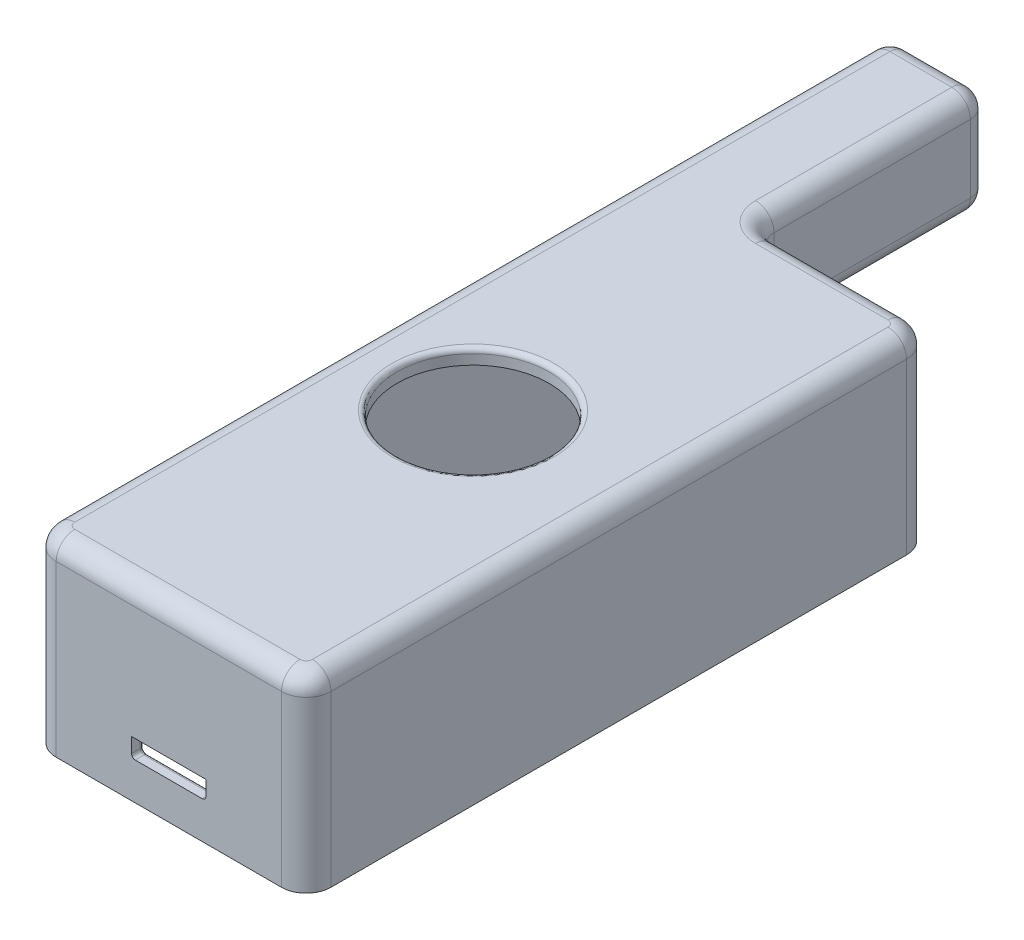
SolidWorks part; units mm, degrees
ref_plane "Front Plane" through (0, 0, 0) normal (0, 0, 1) x (1, 0, 0)
ref_plane "Top Plane" through (0, 0, 0) normal (0, 1, 0) x (1, 0, 0)
ref_plane "Right Plane" through (0, 0, 0) normal (1, 0, 0) x (0, 0, -1)
sketch "Esquisse1" plane through (0, 0, 0) normal (0, 1, 0) x (1, 0, 0)
  line L0 (-10.0853, 24.1442) -> (-10.0853, 42.1442)
  line L1 (-3.0853, 24.2853) -> (9.1147, 24.2853)
  line L2 (-10.0853, 24.1442) -> (-10.0853, -23.2147)
  line L3 (-9.0853, -24.2147) -> (9.1147, -24.2147)
  line L4 (10.1147, 23.2853) -> (10.1147, -23.2147)
  line L5 (-10.0853, 24.1442) -> (10.1147, -24.2147) construction
  line L6 (-10.0853, -24.2147) -> (10.1147, 24.2853) construction
  line L7 (-9.0853, 43.1442) -> (-5.0853, 43.1442)
  line L8 (-4.0853, 42.1442) -> (-4.0853, 25.2853)
  line L9 (-11.0853, 24.1442) -> (-11.0853, 42.1442)
  line L10 (-9.0853, 44.1442) -> (-5.0853, 44.1442)
  line L11 (-3.0853, 42.1442) -> (-3.0853, 27.2853)
  line L12 (-1.0853, 25.2853) -> (9.1147, 25.2853)
  line L13 (11.1147, 23.2853) -> (11.1147, -23.2147)
  line L14 (-9.0853, -25.2147) -> (9.1147, -25.2147)
  line L15 (-11.0853, 24.1442) -> (-11.0853, -23.2147)
  line L16 (-10.0853, 42.1442) -> (-10.0853, 43.1442)
  line L17 (-10.0853, 43.1442) -> (-9.0853, 43.1442)
  line L18 (-4.0853, 42.1442) -> (-4.0853, 43.1442)
  line L19 (-4.0853, 43.1442) -> (-5.0853, 43.1442)
  line L20 (-11.0853, 42.1442) -> (-11.0853, 44.1442)
  line L21 (-11.0853, 44.1442) -> (-9.0853, 44.1442)
  line L22 (-3.0853, 42.1442) -> (-3.0853, 44.1442)
  line L23 (-3.0853, 44.1442) -> (-5.0853, 44.1442)
  arc A0 (-10.0853, -23.2147) -> (-9.0853, -24.2147) centre (-9.0853, -23.2147) ccw
  arc A1 (9.1147, -24.2147) -> (10.1147, -23.2147) centre (9.1147, -23.2147) ccw
  arc A2 (9.1147, 24.2853) -> (10.1147, 23.2853) centre (9.1147, 23.2853) cw
  arc A3 (-4.0853, 25.2853) -> (-3.0853, 24.2853) centre (-3.0853, 25.2853) ccw
  arc A9 (9.1147, 25.2853) -> (11.1147, 23.2853) centre (9.1147, 23.2853) cw
  arc A10 (9.1147, -25.2147) -> (11.1147, -23.2147) centre (9.1147, -23.2147) ccw
  arc A11 (-11.0853, -23.2147) -> (-9.0853, -25.2147) centre (-9.0853, -23.2147) ccw
  arc A12 (-3.0853, 27.2853) -> (-1.0853, 25.2853) centre (-1.0853, 27.2853) ccw
  point P0 (0, 0)
  point P22 (-4.0853, 43.1442)
  point P25 (-10.0853, 43.1442)
  dimension "D5" = 1
  dimension "D7" = 2
  dimension "D1" = 20.2
  dimension "D2" = 48.5
  dimension "D3" = 19
  dimension "D4" = 6
extrude "Boss.-Extru.1" add sketch "Esquisse1" along normal blind 14
sketch "Esquisse2" plane through (0, 14, 0) normal (0, 1, 0) x (1, 0, 0)
  line L12 (-11.0853, 44.1442) -> (-11.0853, -23.2147)
  line L13 (-9.0853, -25.2147) -> (9.1147, -25.2147)
  line L14 (11.1147, -23.2147) -> (11.1147, 23.2853)
  line L15 (9.1147, 25.2853) -> (-1.0853, 25.2853)
  line L16 (-3.0853, 27.2853) -> (-3.0853, 44.1442)
  line L17 (-3.0853, 44.1442) -> (-11.0853, 44.1442)
  line L18 (-11.0853, 44.1442) -> (-11.0853, -23.2147)
  line L19 (-9.0853, -25.2147) -> (9.1147, -25.2147)
  line L20 (11.1147, -23.2147) -> (11.1147, 23.2853)
  line L21 (9.1147, 25.2853) -> (-1.0853, 25.2853)
  line L22 (-3.0853, 27.2853) -> (-3.0853, 44.1442)
  line L23 (-3.0853, 44.1442) -> (-11.0853, 44.1442)
  arc A12 (-11.0853, -23.2147) -> (-9.0853, -25.2147) centre (-9.0853, -23.2147) ccw
  arc A13 (9.1147, -25.2147) -> (11.1147, -23.2147) centre (9.1147, -23.2147) ccw
  arc A14 (11.1147, 23.2853) -> (9.1147, 25.2853) centre (9.1147, 23.2853) ccw
  arc A15 (-3.0853, 27.2853) -> (-1.0853, 25.2853) centre (-1.0853, 27.2853) ccw
  arc A18 (-11.0853, -23.2147) -> (-9.0853, -25.2147) centre (-9.0853, -23.2147) ccw
  arc A19 (9.1147, -25.2147) -> (11.1147, -23.2147) centre (9.1147, -23.2147) ccw
  arc A20 (11.1147, 23.2853) -> (9.1147, 25.2853) centre (9.1147, 23.2853) ccw
  arc A21 (-3.0853, 27.2853) -> (-1.0853, 25.2853) centre (-1.0853, 27.2853) ccw
  dimension "D1" = 0
extrude "Boss.-Extru.2" add sketch "Esquisse2" along normal blind 1.2
sketch "Esquisse4" plane through (0, 14, 0) normal (0, -1, 0) x (1, 0, 0)
  line L0 (-10.0853, -0.7153) -> (-1.3353, -0.7153) construction
  line L1 (-10.0853, -43.1442) -> (-10.0853, 23.2147) construction
  line L2 (-1.3353, -0.7153) -> (-1.3353, 24.2147) construction
  line L3 (-9.0853, 24.2147) -> (9.1147, 24.2147) construction
  circle A0 centre (-1.3353, -0.7153) radius 6.15
  dimension "D3" = 12.3
  dimension "D1" = 24.93
  dimension "D2" = 8.75
extrude "Enlèv. mat.-Extru.1" cut sketch "Esquisse4" against normal through all
fillet "Congé2" radius 0.4 1 edges at (-1.3353, 15.2, -6.8653)
sketch "Esquisse5" plane through (0, 14, 0) normal (0, -1, 0) x (1, 0, 0)
  line L0 (-10.0853, 18.0529) -> (-9.8853, 18.0529)
  line L1 (-10.0853, -43.1442) -> (-10.0853, 23.2147) construction
  line L2 (-8.8853, 19.0529) -> (-8.8853, 22.0147)
  line L3 (-7.8853, 23.0147) -> (-3.7713, 23.0147)
  line L4 (-2.7713, 24.0147) -> (-2.7713, 24.7437)
  line L5 (-2.7713, 24.7437) -> (-9.6289, 24.7437)
  line L6 (-9.6289, 24.7437) -> (-10.48, 23.5517)
  line L7 (-10.48, 23.5517) -> (-10.48, 18.0529)
  line L8 (-10.48, 18.0529) -> (-10.0853, 18.0529)
  line L9 (-10.0853, -43.1442) -> (-10.0853, 23.2147) construction
  line L10 (-9.0853, 24.2147) -> (9.1147, 24.2147) construction
  arc A0 (-3.7713, 23.0147) -> (-2.7713, 24.0147) centre (-3.7713, 24.0147) ccw
  arc A1 (-9.8853, 18.0529) -> (-8.8853, 19.0529) centre (-9.8853, 19.0529) ccw
  arc A2 (-8.8853, 22.0147) -> (-7.8853, 23.0147) centre (-7.8853, 22.0147) cw
  dimension "D3" = 1
  dimension "D1" = 1.2
  dimension "D2" = 1.2
extrude "Boss.-Extru.3" add sketch "Esquisse5" along normal blind 5.6
sketch "Esquisse6" plane through (0, 14, 0) normal (0, -1, 0) x (1, 0, 0)
  line L0 (0, 0) -> (0, -17.4052) construction
  line L2 (-4, -12.4052) -> (4, -12.4052)
  line L3 (-5, -13.4052) -> (-5, -21.4052)
  line L4 (-4, -22.4052) -> (4, -22.4052)
  line L5 (5, -13.4052) -> (5, -21.4052)
  line L6 (-5, -12.4052) -> (5, -22.4052) construction
  line L7 (-5, -22.4052) -> (5, -12.4052) construction
  arc A0 (-5, -21.4052) -> (-4, -22.4052) centre (-4, -21.4052) ccw
  arc A1 (4, -22.4052) -> (5, -21.4052) centre (4, -21.4052) ccw
  arc A2 (4, -12.4052) -> (5, -13.4052) centre (4, -13.4052) cw
  arc A3 (-4, -12.4052) -> (-5, -13.4052) centre (-4, -13.4052) ccw
  dimension "D3" = 1
  dimension "D1" = 10
  dimension "D2" = 10
extrude "Boss.-Extru.4" add sketch "Esquisse6" along normal blind 2.11
sketch "Esquisse8" plane through (0, 0, 0) normal (0, -1, 0) x (1, 0, 0)
  line L0 (-1.0853, -25.2853) -> (-11.0853, -25.2853)
  line L1 (-11.0853, -44.1442) -> (-11.0853, 23.2147) construction
  line L2 (-11.0853, -25.2853) -> (-11.0853, -45.1388)
  line L3 (-11.0853, -45.1388) -> (-1.0853, -45.1388)
  line L4 (-1.0853, -45.1388) -> (-1.0853, -25.2853)
extrude "Enlèv. mat.-Extru.2" cut sketch "Esquisse8" against normal offset from surface (8 mm away) 6 up to face at (-2.338, 14, 2.2145)
sketch "Esquisse9" plane through (0, 0, 0) normal (0, -1, 0) x (1, 0, 0)
  line L0 (9.1147, -24.2853) -> (-3.0853, -24.2853) construction
  line L1 (-11.0853, -25.2853) -> (-0.5832, -25.2853)
  line L2 (-11.0853, -25.2853) -> (-11.0853, -24.2853)
  line L3 (-11.0853, -24.2853) -> (-0.5832, -24.2853)
  line L4 (-0.5832, -25.2853) -> (-0.5832, -24.2853)
extrude "Boss.-Extru.5" add sketch "Esquisse9" against normal up to surface (14 mm away) up to face at (-2.338, 14, 2.2145)
sketch "Esquisse10" plane through (0, 0, -25.2853) normal (0, 0, -1) x (-1, 0, 0)
  line L0 (7.0853, 14) -> (7.0853, 11.0599) construction
  line L1 (10.0853, 14) -> (4.0853, 14) construction
  line L3 (11.0853, 8) -> (11.0853, 6.6914)
  line L4 (11.0853, 15.2) -> (11.0853, 0) construction
  line L5 (11.0853, 6.6914) -> (3.0853, 6.6914)
  line L6 (3.0853, 6.6914) -> (3.0853, 8)
  line L7 (11.0853, 8) -> (11.0853, 11.0599)
  line L8 (11.0853, 11.0599) -> (10.1452, 11.0599)
  line L9 (3.0853, 8) -> (3.0853, 11.0599)
  line L10 (3.0853, 15.2) -> (3.0853, 8) construction
  line L11 (3.0853, 11.0599) -> (4.0254, 11.0599)
  arc A0 (4.0254, 11.0599) -> (10.1452, 11.0599) centre (7.0853, 11.0599) ccw
extrude "Boss.-Extru.6" add sketch "Esquisse10" along normal up to surface (18.8588 mm away) up to face at (-7.0853, 11.6, -44.1442)
sketch "Esquisse11" plane through (0, 8, 0) normal (0, -1, 0) x (1, 0, 0)
  line L4 (-3.0853, -25.2853) -> (-3.0853, -27.2853)
  line L5 (-1.0853, -25.2853) -> (-3.0853, -25.2853)
  line L6 (-3.0853, -25.2853) -> (-3.0853, -27.2853)
  line L7 (-1.0853, -25.2853) -> (-3.0853, -25.2853)
  arc A2 (-1.0853, -25.2853) -> (-3.0853, -27.2853) centre (-1.0853, -27.2853) ccw
  arc A3 (-1.0853, -25.2853) -> (-3.0853, -27.2853) centre (-1.0853, -27.2853) ccw
  dimension "D1" = 0
extrude "Enlèv. mat.-Extru.3" cut sketch "Esquisse11" against normal through all
sketch "Esquisse12" plane through (0, 0, -25.2853) normal (0, 0, -1) x (-1, 0, 0)
  line L6 (10.0853, 10.4575) -> (10.0853, 14)
  line L7 (10.0853, 14) -> (4.0853, 14)
  line L8 (4.0853, 14) -> (4.0853, 10.4575)
  line L9 (10.0853, 10.4575) -> (10.0853, 14)
  line L10 (10.0853, 14) -> (4.0853, 14)
  line L11 (4.0853, 14) -> (4.0853, 10.4575)
  arc A2 (4.0853, 10.4575) -> (10.0853, 10.4575) centre (7.0853, 11.0599) ccw
  arc A3 (4.0853, 10.4575) -> (10.0853, 10.4575) centre (7.0853, 11.0599) ccw
  dimension "D1" = 0
extrude "Enlèv. mat.-Extru.4" cut sketch "Esquisse12" against normal blind 1
fillet "Congé3" radius 1.5 3 edges at (-3.0853, 10.9457, -25.2853) (-11.0853, 10.9457, -44.1442) (-3.0853, 10.9457, -44.1442)
fillet "Congé4" radius 1.5 7 edges at (-2.6459, 6.6914, -25.7247) (-3.0853, 6.6914, -34.7148) (-3.5246, 6.6914, -43.7048) (-7.0853, 6.6914, -44.1442) (-10.6459, 6.6914, -43.7048) (-11.0853, 3.3457, -25.2853) (-11.0853, 6.6914, -33.9648)
fillet "Congé5" radius 1.5 12 edges at (10.5289, 15.2, 24.6289) (0.0147, 15.2, 25.2147) (-10.4995, 15.2, 24.6289) (-11.0853, 15.2, -9.7148) (-10.6459, 15.2, -43.7048) (-7.0853, 15.2, -44.1442) (-3.5246, 15.2, -43.7048) (-3.0853, 15.2, -34.7148) (-2.6459, 15.2, -25.7247) (3.7647, 15.2, -25.2853) (10.5289, 15.2, -24.6996) (11.1147, 15.2, -0.0353)
fillet "Congé6" radius 0.5 7 edges at (2.5147, 14, -24.2853) (9.8218, 14, -23.9924) (10.1147, 14, -0.0353) (9.8218, 14, 23.9218) (-4.0853, 14, -33.7148) (3.1717, 14, 24.2147) (-10.0853, 14, -12.5456)
sketch "Esquisse13" plane through (0, 0, 25.2147) normal (0, 0, 1) x (1, 0, 0)
  line L0 (0.0147, 13.7) -> (0, 0) construction
  line L1 (-2.9952, 4.5) -> (3.0048, 4.5)
  line L2 (-2.9952, 4.5) -> (-2.9952, 3.3)
  line L3 (-2.6952, 3) -> (2.7048, 3)
  line L4 (3.0048, 4.5) -> (3.0048, 3.3)
  line L5 (9.1147, 13.7) -> (-9.0853, 13.7) construction
  line L6 (-9.0853, 0) -> (9.1147, 0) construction
  arc A0 (2.7048, 3) -> (3.0048, 3.3) centre (2.7048, 3.3) ccw
  arc A1 (-2.9952, 3.3) -> (-2.6952, 3) centre (-2.6952, 3.3) ccw
  point P9 (0.0048, 4.5)
  point P14 (3.0048, 3)
  dimension "D4" = 0.3
  dimension "D1" = 1.5
  dimension "D2" = 6
  dimension "D3" = 3
extrude "Enlèv. mat.-Extru.5" cut sketch "Esquisse13" against normal through all
fillet "Congé7" radius 0.3 10 edges at (3.0048, 3.9, 24.2147) (2.917, 3.0879, 24.2147) (-2.9952, 3.9, 24.2147) (-2.9073, 3.0879, 24.2147) (-2.9952, 3.9, -24.2853) (-2.9073, 3.0879, -24.2853) (3.0048, 3.9, -24.2853) (2.917, 3.0879, -24.2853) (0.0048, 3, 24.2147) (0.0048, 3, -24.2853)
